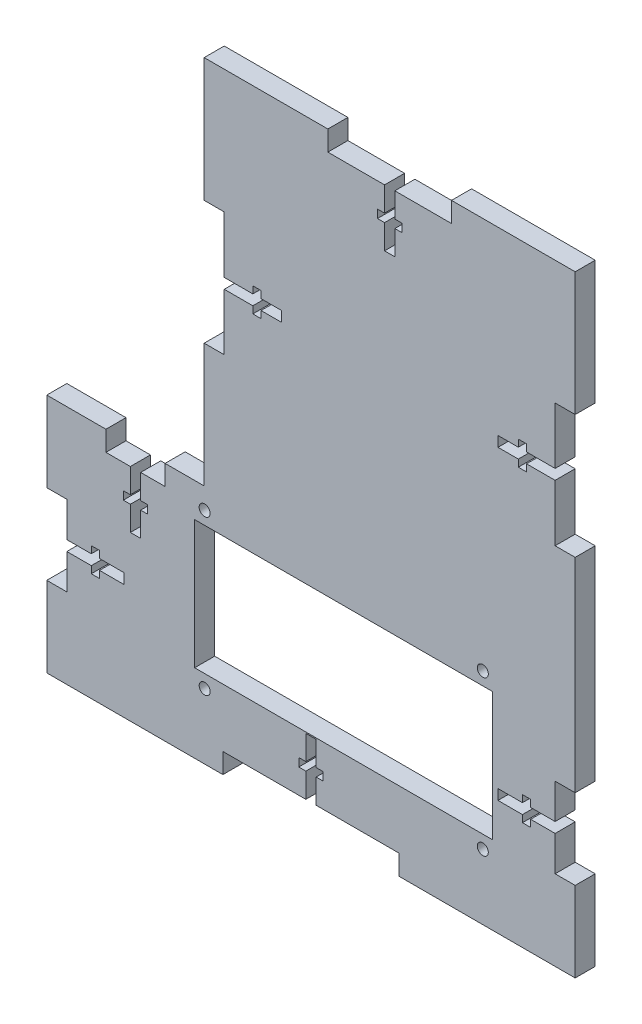
SolidWorks part; units mm, degrees
ref_plane "Front Plane" through (0, 0, 0) normal (0, 0, 1) x (1, 0, 0)
ref_plane "Top Plane" through (0, 0, 0) normal (0, 1, 0) x (1, 0, 0)
ref_plane "Right Plane" through (0, 0, 0) normal (1, 0, 0) x (0, 0, -1)
sketch "Sketch1" plane through (0, 0, 0) normal (0, 0, 1) x (1, 0, 0)
  line L1 (-66.929, -30.48) -> (66.929, -30.48)
  line L2 (-66.929, -30.48) -> (-66.929, 30.48)
  line L3 (-66.929, 30.48) -> (66.929, 30.48)
  line L4 (66.929, -30.48) -> (66.929, 30.48)
  line L5 (-66.929, -30.48) -> (66.929, 30.48) construction
  line L6 (-66.929, 30.48) -> (66.929, -30.48) construction
  point P0 (0, 0)
  dimension "D1" = 133.858
  dimension "D2" = 60.96
extrude "Boss-Extrude1" add sketch "Sketch1" along normal blind 5.08
sketch "Sketch2" plane through (0, 0, 5.08) normal (0, 0, 1) x (1, 0, 0)
  line L1 (-51.943, 30.48) -> (-36.957, 30.48)
  line L2 (-51.943, 30.48) -> (-51.943, 25.4)
  line L3 (-51.943, 25.4) -> (-36.957, 25.4)
  line L4 (-36.957, 30.48) -> (-36.957, 25.4)
  line L5 (66.929, 30.48) -> (-66.929, 30.48) construction
  line L6 (0, 0) -> (66.929, 0) construction
  line L7 (66.929, -30.48) -> (66.929, 30.48) construction
  dimension "D1" = 14.986
  dimension "D2" = 5.08
  dimension "D3" = 14.986
extrude "Cut-Extrude1" cut sketch "Sketch2" against normal through all
sketch "Sketch3" plane through (0, 0, 5.08) normal (0, 0, 1) x (1, 0, 0)
  line L0 (-66.929, 30.48) -> (-66.929, -30.48) construction
  line L1 (-66.929, 10.16) -> (-61.849, 10.16)
  line L2 (-66.929, 10.16) -> (-66.929, -10.16)
  line L3 (-66.929, -10.16) -> (-61.849, -10.16)
  line L4 (-61.849, 10.16) -> (-61.849, -10.16)
  line L5 (0, 0) -> (0, 39.951) construction
  line L6 (66.929, -10.16) -> (61.849, -10.16)
  line L7 (66.929, 10.16) -> (66.929, -10.16)
  line L8 (66.929, 10.16) -> (61.849, 10.16)
  line L9 (61.849, 10.16) -> (61.849, -10.16)
  dimension "D1" = 5.08
  dimension "D2" = 20.32
  dimension "D3" = 20.32
extrude "Cut-Extrude2" cut sketch "Sketch3" against normal through all
sketch "Sketch4" plane through (0, 0, 5.08) normal (0, 0, 1) x (1, 0, 0)
  line L0 (0, 0) -> (-61.849, 0) construction
  line L1 (-61.849, -10.16) -> (-61.849, 10.16) construction
  line L2 (0, 0) -> (0, 28.5152) construction
  line L3 (-61.849, 1.3017) -> (-47.371, 1.3017)
  line L4 (-61.849, 1.3017) -> (-61.849, -1.3018)
  line L5 (-61.849, -1.3018) -> (-47.371, -1.3018)
  line L6 (-47.371, 1.3017) -> (-47.371, -1.3018)
  line L7 (47.371, 1.3018) -> (47.371, -1.3018)
  line L8 (61.849, -1.3017) -> (47.371, -1.3018)
  line L9 (61.849, 1.3017) -> (61.849, -1.3017)
  line L10 (61.849, 1.3017) -> (47.371, 1.3018)
  line L11 (-66.929, -10.16) -> (-66.929, 10.16) construction
  point P9 (-47.371, 0)
  dimension "D1" = 1.3017
  dimension "D2" = 19.558
extrude "Cut-Extrude3" cut sketch "Sketch4" against normal through all
sketch "Sketch5" plane through (0, 0, 5.08) normal (0, 0, 1) x (1, 0, 0)
  line L0 (-44.45, 25.4) -> (-44.45, 4.7969) construction
  line L1 (-51.943, 25.4) -> (-36.957, 25.4) construction
  line L2 (0, 0) -> (35.9654, 0) construction
  line L3 (-43.1482, 25.4) -> (-45.7518, 25.4)
  line L4 (-43.1482, 25.4) -> (-43.1483, 10.922)
  line L5 (-43.1483, 10.922) -> (-45.7518, 10.922)
  line L6 (-45.7518, 25.4) -> (-45.7518, 10.922)
  point P11 (-44.45, 25.4)
  dimension "D1" = 2.6035
  dimension "D3" = 14.478
extrude "Cut-Extrude4" cut sketch "Sketch5" against normal through all
sketch "Sketch6" plane through (0, 0, 5.08) normal (0, 0, 1) x (1, 0, 0)
  line L0 (-54.61, 1.3017) -> (-54.61, -1.3018) construction
  line L1 (-47.371, 1.3017) -> (-61.849, 1.3017) construction
  line L2 (-61.849, -1.3018) -> (-47.371, -1.3018) construction
  line L3 (-43.1483, 18.161) -> (-45.7518, 18.161) construction
  line L4 (-43.1482, 25.4) -> (-43.1483, 10.922) construction
  line L5 (-45.7518, 10.922) -> (-45.7518, 25.4) construction
  line L6 (-43.1483, 18.161) -> (-47.5361, 18.161) construction
  line L7 (-47.5361, 19.2024) -> (-41.3639, 19.2024)
  line L8 (-47.5361, 19.2024) -> (-47.5361, 17.1196)
  line L9 (-47.5361, 17.1196) -> (-41.3639, 17.1196)
  line L10 (-41.3639, 19.2024) -> (-41.3639, 17.1196)
  line L11 (0, 0) -> (19.2929, 0) construction
  line L12 (0, 0) -> (0, 14.5303) construction
  line L17 (-54.61, -1.3018) -> (-54.61, -3.0861) construction
  line L18 (-55.6514, 3.0861) -> (-53.5686, 3.0861)
  line L19 (-55.6514, 3.0861) -> (-55.6514, -3.0861)
  line L20 (-55.6514, -3.0861) -> (-53.5686, -3.0861)
  line L21 (-53.5686, 3.0861) -> (-53.5686, -3.0861)
  line L22 (-44.45, 10.922) -> (-44.45, 17.1196) construction
  line L23 (-43.1483, 10.922) -> (-45.7518, 10.922) construction
  line L24 (-47.371, 0) -> (-53.5686, 0) construction
  line L25 (-47.371, -1.3018) -> (-47.371, 1.3017) construction
  line L26 (55.6514, -3.0861) -> (53.5686, -3.0861)
  line L27 (53.5686, 3.0861) -> (53.5686, -3.0861)
  line L28 (55.6514, 3.0861) -> (55.6514, -3.0861)
  line L29 (55.6514, 3.0861) -> (53.5686, 3.0861)
  dimension "D1" = 6.1722
  dimension "D2" = 2.0828
  dimension "D3" = 2.0828
  dimension "D4" = 6.1722
extrude "Cut-Extrude5" cut sketch "Sketch6" against normal through all
sketch "Sketch7" plane through (0, 0, 5.08) normal (0, 0, 1) x (1, 0, 0)
  line L0 (66.929, 30.48) -> (66.929, 124.46)
  line L1 (66.929, 124.46) -> (-27.051, 124.46)
  line L2 (-27.051, 124.46) -> (-27.051, 30.48)
  line L3 (66.929, 30.48) -> (-36.957, 30.48) construction
  line L60 (-43.1482, 19.2024) -> (-41.3639, 19.2024)
  line L61 (-41.3639, 19.2024) -> (-41.3639, 17.1196)
  line L62 (-41.3639, 17.1196) -> (-43.1482, 17.1196)
  line L63 (-43.1482, 10.922) -> (-45.7518, 10.922)
  line L64 (-45.7518, 17.1196) -> (-47.5361, 17.1196)
  line L65 (-47.5361, 17.1196) -> (-47.5361, 19.2024)
  line L66 (-47.5361, 19.2024) -> (-45.7518, 19.2024)
  line L67 (-45.7518, 25.4) -> (-51.943, 25.4)
  line L68 (-43.1482, 25.4) -> (-43.1482, 19.2024)
  line L70 (-43.1482, 17.1196) -> (-43.1482, 10.922)
  line L72 (61.849, -1.3018) -> (55.6514, -1.3018)
  line L73 (55.6514, -1.3018) -> (55.6514, -3.0861)
  line L74 (55.6514, -3.0861) -> (53.5686, -3.0861)
  line L75 (53.5686, -3.0861) -> (53.5686, -1.3017)
  line L76 (53.5686, -1.3017) -> (47.371, -1.3017)
  line L77 (47.371, -1.3017) -> (47.371, 1.3018)
  line L78 (47.371, 1.3018) -> (53.5686, 1.3018)
  line L79 (53.5686, 1.3018) -> (53.5686, 3.0861)
  line L80 (53.5686, 3.0861) -> (55.6514, 3.0861)
  line L81 (55.6514, 3.0861) -> (55.6514, 1.3018)
  line L82 (55.6514, 1.3018) -> (61.849, 1.3018)
  line L83 (61.849, 1.3018) -> (61.849, 10.16)
  line L84 (61.849, 10.16) -> (66.929, 10.16)
  line L85 (66.929, 10.16) -> (66.929, 30.48)
  line L86 (66.929, 30.48) -> (-36.957, 30.48)
  line L87 (-36.957, 30.48) -> (-36.957, 25.4)
  line L88 (-36.957, 25.4) -> (-43.1482, 25.4)
  line L89 (-45.7518, 10.922) -> (-45.7518, 17.1196)
  line L91 (-45.7518, 19.2024) -> (-45.7518, 25.4)
  line L101 (-51.943, 25.4) -> (-51.943, 30.48)
  line L102 (-51.943, 30.48) -> (-66.929, 30.48)
  line L103 (-66.929, 30.48) -> (-66.929, 10.16)
  line L104 (-66.929, 10.16) -> (-61.849, 10.16)
  line L105 (-61.849, 10.16) -> (-61.849, 1.3017)
  line L106 (-61.849, 1.3017) -> (-55.6514, 1.3017)
  line L107 (-55.6514, 1.3017) -> (-55.6514, 3.0861)
  line L108 (-55.6514, 3.0861) -> (-53.5686, 3.0861)
  line L109 (-53.5686, 3.0861) -> (-53.5686, 1.3017)
  line L110 (-53.5686, 1.3017) -> (-47.371, 1.3017)
  line L111 (-47.371, 1.3017) -> (-47.371, -1.3018)
  line L112 (-47.371, -1.3018) -> (-53.5686, -1.3018)
  line L113 (-53.5686, -1.3018) -> (-53.5686, -3.0861)
  line L114 (-53.5686, -3.0861) -> (-55.6514, -3.0861)
  line L115 (-55.6514, -3.0861) -> (-55.6514, -1.3018)
  line L116 (-55.6514, -1.3018) -> (-61.849, -1.3018)
  line L117 (-61.849, -1.3018) -> (-61.849, -10.16)
  line L118 (-61.849, -10.16) -> (-66.929, -10.16)
  line L119 (-66.929, -10.16) -> (-66.929, -30.48)
  line L120 (-66.929, -30.48) -> (66.929, -30.48)
  line L137 (66.929, -30.48) -> (66.929, -10.16)
  line L138 (66.929, -10.16) -> (61.849, -10.16)
  line L139 (61.849, -10.16) -> (61.849, -1.3018)
  line L154 (66.929, 30.48) -> (-27.051, 30.48)
  dimension "D1" = 93.98
  dimension "D2" = 93.98
  dimension "D3" = 0
extrude "Boss-Extrude2" add sketch "Sketch7" against normal blind 5.08
sketch "Sketch8" plane through (0, 0, 5.08) normal (0, 0, 1) x (1, 0, 0)
  line L0 (-66.929, -30.48) -> (66.929, -30.48) construction
  line L1 (22.3097, -30.48) -> (-22.3097, -30.48)
  line L2 (22.3097, -30.48) -> (22.3097, -25.4)
  line L3 (22.3097, -25.4) -> (-22.3097, -25.4)
  line L4 (-22.3097, -30.48) -> (-22.3097, -25.4)
  dimension "D1" = 5.08
  dimension "D2" = 44.6193
  dimension "D3" = 44.6193
extrude "Cut-Extrude6" cut sketch "Sketch8" against normal through all
sketch "Sketch10" plane through (0, 0, 5.08) normal (0, 0, 1) x (1, 0, 0)
  line L0 (22.3097, -25.4) -> (-22.3097, -25.4) construction
  line L1 (1.3017, -25.4) -> (-1.3017, -25.4)
  line L2 (1.3017, -25.4) -> (1.3017, -10.922)
  line L3 (1.3017, -10.922) -> (-1.3018, -10.922)
  line L4 (-1.3017, -25.4) -> (-1.3018, -10.922)
  line L5 (0, -10.922) -> (0, 0) construction
  dimension "D1" = 2.6035
  dimension "D2" = 14.478
extrude "Cut-Extrude7" cut sketch "Sketch10" against normal through all
sketch "Sketch11" plane through (0, 0, 5.08) normal (0, 0, 1) x (1, 0, 0)
  line L0 (3.0861, -18.161) -> (3.0861, -25.4) construction
  line L1 (22.3097, -25.4) -> (1.3017, -25.4) construction
  line L2 (-3.0861, -17.1196) -> (3.0861, -17.1196)
  line L3 (-3.0861, -17.1196) -> (-3.0861, -19.2024)
  line L4 (-3.0861, -19.2024) -> (3.0861, -19.2024)
  line L5 (3.0861, -17.1196) -> (3.0861, -19.2024)
  line L6 (-1.3018, -10.922) -> (-1.3018, -25.4) construction
  point P8 (-1.3018, -19.2024)
  dimension "D1" = 2.0828
  dimension "D2" = 6.1722
  dimension "D3" = 7.239
  dimension "D4" = 1.7844
extrude "Cut-Extrude8" cut sketch "Sketch11" against normal through all
sketch "Sketch12" plane through (0, 0, 5.08) normal (0, 0, 1) x (1, 0, 0)
  line L0 (66.929, 10.16) -> (66.929, 124.46) construction
  line L1 (66.929, 61.8067) -> (61.849, 61.8067)
  line L2 (66.929, 61.8067) -> (66.929, 93.1333)
  line L3 (66.929, 93.1333) -> (61.849, 93.1333)
  line L4 (61.849, 61.8067) -> (61.849, 93.1333)
  line L5 (19.939, 124.46) -> (19.939, 42.6911) construction
  line L6 (66.929, 124.46) -> (-27.051, 124.46) construction
  line L7 (-21.971, 61.8067) -> (-21.971, 93.1333)
  line L8 (-27.051, 93.1333) -> (-21.971, 93.1333)
  line L9 (-27.051, 61.8067) -> (-27.051, 93.1333)
  line L10 (-27.051, 61.8067) -> (-21.971, 61.8067)
  dimension "D1" = 5.08
  dimension "D2" = 31.3267
  dimension "D3" = 31.3267
extrude "Cut-Extrude9" cut sketch "Sketch12" against normal through all
sketch "Sketch13" plane through (0, 0, 5.08) normal (0, 0, 1) x (1, 0, 0)
  line L0 (47.371, 77.47) -> (61.849, 77.47) construction
  line L1 (61.849, 93.1333) -> (61.849, 61.8067) construction
  line L2 (19.939, 124.46) -> (19.939, 63.8669) construction
  line L3 (66.929, 124.46) -> (-27.051, 124.46) construction
  line L4 (-21.971, 76.1683) -> (-21.971, 78.7717)
  line L5 (47.371, 76.1683) -> (61.849, 76.1683)
  line L6 (47.371, 76.1683) -> (47.371, 78.7718)
  line L7 (47.371, 78.7718) -> (61.849, 78.7718)
  line L8 (61.849, 76.1683) -> (61.849, 78.7718)
  line L9 (-7.493, 78.7718) -> (-21.971, 78.7717)
  line L10 (-7.493, 76.1683) -> (-7.493, 78.7718)
  line L11 (-7.493, 76.1683) -> (-21.971, 76.1683)
  line L12 (19.939, 130.1398) -> (19.939, 124.46) construction
  line L13 (21.2407, 124.46) -> (18.6373, 124.46)
  line L14 (21.2407, 124.46) -> (21.2408, 104.902)
  line L15 (21.2408, 104.902) -> (18.6373, 104.902)
  line L16 (18.6373, 124.46) -> (18.6373, 104.902)
  dimension "D1" = 2.6035
  dimension "D2" = 14.478
  dimension "D3" = 2.6035
  dimension "D4" = 19.558
extrude "Cut-Extrude10" cut sketch "Sketch13" against normal through all
sketch "Sketch14" plane through (0, 0, 5.08) normal (0, 0, 1) x (1, 0, 0)
  line L0 (54.61, 93.7894) -> (61.849, 93.7894) construction
  line L1 (54.61, 74.3839) -> (52.5272, 74.3839)
  line L2 (54.61, 74.3839) -> (54.61, 80.5561)
  line L3 (54.61, 80.5561) -> (52.5272, 80.5561)
  line L4 (52.5272, 74.3839) -> (52.5272, 80.5561)
  line L5 (61.849, 93.1333) -> (61.849, 78.7718) construction
  line L6 (61.849, 78.7718) -> (47.371, 78.7718) construction
  line L7 (19.939, 124.46) -> (19.939, -38.735) construction
  line L9 (-14.732, 80.5561) -> (-12.6492, 80.5561)
  line L10 (-14.732, 74.3839) -> (-14.732, 80.5561)
  line L11 (-12.6492, 74.3839) -> (-12.6492, 80.5561)
  line L12 (-14.732, 74.3839) -> (-12.6492, 74.3839)
  line L14 (21.2407, 124.46) -> (18.6373, 124.46) construction
  line L15 (18.6373, 124.46) -> (18.6373, 104.902) construction
  line L16 (23.0251, 111.0996) -> (16.8529, 111.0996)
  line L17 (23.0251, 111.0996) -> (23.0251, 113.1824)
  line L18 (23.0251, 113.1824) -> (16.8529, 113.1824)
  line L19 (16.8529, 111.0996) -> (16.8529, 113.1824)
  line L20 (16.8529, 112.141) -> (16.8529, 124.46) construction
  line L21 (18.6373, 124.46) -> (-27.051, 124.46) construction
  point P8 (52.5272, 78.7718)
  point P25 (18.6373, 111.0996)
  dimension "D1" = 2.0828
  dimension "D2" = 6.1722
  dimension "D3" = 7.239
  dimension "D4" = 1.7844
  dimension "D5" = 2.0828
  dimension "D6" = 6.1722
  dimension "D7" = 1.7844
  dimension "D8" = 12.319
extrude "Cut-Extrude11" cut sketch "Sketch14" against normal through all
sketch "Sketch15" plane through (0, 0, 5.08) normal (0, 0, 1) x (1, 0, 0)
  line L0 (66.929, 124.46) -> (21.2407, 124.46) construction
  line L1 (35.6023, 124.46) -> (4.2757, 124.46)
  line L2 (35.6023, 124.46) -> (35.6023, 119.38)
  line L3 (35.6023, 119.38) -> (4.2757, 119.38)
  line L4 (4.2757, 124.46) -> (4.2757, 119.38)
  dimension "D1" = 5.08
  dimension "D2" = 31.3267
  dimension "D3" = 31.3267
extrude "Cut-Extrude12" cut sketch "Sketch15" against normal through all
sketch "Sketch16" plane through (0, 0, 0) normal (0, 0, 1) x (1, 0, 0)
  line L0 (-44.7108, 14.9648) -> (-29.4708, 14.9648) construction
  line L1 (-29.4708, 21.8935) -> (45.9672, 21.8935)
  line L2 (-29.4708, 21.8935) -> (-29.4708, -10.6185)
  line L3 (-29.4708, -10.6185) -> (45.9672, -10.6185)
  line L4 (45.9672, 21.8935) -> (45.9672, -10.6185)
  line L6 (-7.2808, 52.3735) -> (-7.2808, 21.8935) construction
  line L8 (-26.9308, 25.1955) -> (-26.9308, 21.8935) construction
  line L9 (-29.4708, 5.6375) -> (45.9672, 5.6375) construction
  line L10 (43.5288, 25.1955) -> (43.5288, 21.8935) construction
  line L11 (-26.9308, 25.1955) -> (43.5288, 25.1955) construction
  circle A0 centre (-26.9308, 25.1955) radius 1.397
  circle A1 centre (43.5288, 25.1955) radius 1.397
  circle A2 centre (43.5288, -13.9205) radius 1.397
  circle A3 centre (-26.9308, -13.9205) radius 1.397
  dimension "D5" = 2.794
  dimension "D7" = 2.794
  dimension "D1" = 15.24
  dimension "D2" = 30.48
  dimension "D3" = 75.438
  dimension "D4" = 32.512
  dimension "D6" = 3.302
  dimension "D8" = 70.4596
  dimension "D9" = 2.54
extrude "Cut-Extrude14" cut sketch "Sketch16" against normal through all from surface starting at face at (1.6252, 38.6554, 5.08)
equation "\"Length\"= \"Length@Box.SLDASM\""
equation "\"D1@Sketch1\"  = \"Length\" + 2 * \"Material\""
equation "\"Width\"= \"Short Height@Box.SLDASM\""
equation "\"D2@Sketch1\" = \"Width\" + 2 * \"Material\""
equation "\"Material\"= \"Material@Box.SLDASM\""
equation "\"D1@Boss-Extrude1\" = \"Material\""
equation "\"D1@Sketch2\"=(\"Length\" -\"Over Hang@Box.SLDASM\"+\"Material\"*2)/3"
equation "\"D2@Sketch2\"= \"Material\""
equation "\"D3@Sketch2\"=(\"Length\" -\"Over Hang@Box.SLDASM\"+\"Material\"*2)/3"
equation "\"D1@Sketch3\"=\"Material\""
equation "\"D2@Sketch3\"=(\"Width\" +\"Material\"*2)/3"
equation "\"D3@Sketch3\"=(\"Width\" +\"Material\"*2)/3"
equation "\"Diameter of Screw\"= \"Diameter of Screw@Box.SLDASM\""
equation "\"Length of screw\"= \"Length of Screw@Box.SLDASM\""
equation "\"D3@Sketch5\"= \"Length of screw\" - \"Material\""
equation "\"D1@Sketch5\" = \"Diameter of Screw\""
equation "\"D1@Sketch4\"= \"Diameter of Screw\" /2"
equation "\"D2@Sketch4\"=\"Length of screw\""
equation "\"Diameter of Nut\"= \"Diameter of Nut@Box.SLDASM\""
equation "\"D1@Sketch6\"=\"Diameter of Nut\""
equation "\"Height of Nut\"= \"Height of Nut@Box.SLDASM\""
equation "\"D3@Sketch6\"= \"Height of Nut\""
equation "\"D4@Sketch6\"=\"Diameter of Nut\""
equation "\"D2@Sketch6\"=\"Height of Nut\""
equation "\"D1@Sketch7\"= \"Long Height@Box.SLDASM\"-\"Short Height@Box.SLDASM\""
equation "\"D2@Sketch7\" = \"Over Hang@Box.SLDASM\" + \"Material\""
equation "\"D1@Boss-Extrude2\" = \"Material\""
equation "\"D1@Sketch8\"= \"Material\""
equation "\"D2@Sketch8\"=(\"Length\" + \"Material\"*2)/3"
equation "\"D3@Sketch8\"=(\"Length\" + \"Material\"*2)/3"
equation "\"D1@Sketch10\"=\"Diameter of Screw\""
equation "\"D2@Sketch10\"=\"Length of screw\" - \"Material\""
equation "\"D3@Sketch11\" = ( \"Length of screw\" - \"Material\" ) / 2"
equation "\"D4@Sketch11\"= ( \"Diameter of Nut\"-\"Diameter of Screw\" )/2"
equation "\"D1@Sketch12\"=\"Material\""
equation "\"D2@Sketch12\"=(\"Long Height@Box.SLDASM\"-\"Short Height@Box.SLDASM\")/3"
equation "\"D3@Sketch12\"=(\"Long Height@Box.SLDASM\"-\"Short Height@Box.SLDASM\")/3"
equation "\"D1@Sketch13\"=\"Diameter of Screw\""
equation "\"D2@Sketch13\"=\"Length of screw\"-\"Material\""
equation "\"D1@Sketch14\"=\"Height of Nut\""
equation "\"D2@Sketch14\"=\"Diameter of Nut\""
equation "\"D3@Sketch14\"=(\"Length of screw\"-\"Material\")/2"
equation "\"D4@Sketch14\"=(\"Diameter of Nut\"-\"Diameter of Screw\")/2"
equation "\"D1@Sketch15\"= \"Material\""
equation "\"D2@Sketch15\"=(\"Material\"+ \"over hang@Box.SLDASM\" )/3"
equation "\"D3@Sketch15\"=(\"Material\" + \"over hang@Box.SLDASM\" )/3"
equation "\"D3@Sketch13\"=\"Diameter of Screw\""
equation "\"D4@Sketch13\"=\"Length of screw\""
equation "\"D5@Sketch14\"=\"Height of Nut\""
equation "\"D6@Sketch14\"=\"Diameter of Nut\""
equation "\"D7@Sketch14\"=(\"Diameter of Nut\"-\"Diameter of Screw\")/2"
equation "\"D8@Sketch14\"=(\"Length of screw\"-\"Material\")/2 + \"Material\""
